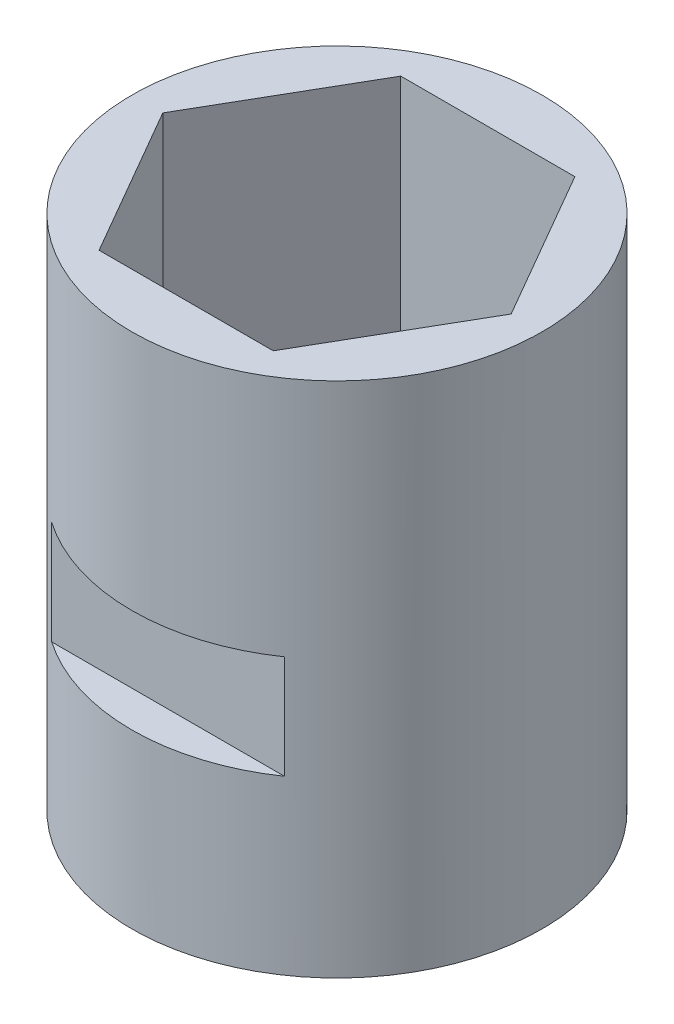
SolidWorks part; units mm, degrees
ref_plane "Front Plane" through (0, 0, 0) normal (0, 0, 1) x (1, 0, 0)
ref_plane "Top Plane" through (0, 0, 0) normal (0, 1, 0) x (1, 0, 0)
ref_plane "Right Plane" through (0, 0, 0) normal (1, 0, 0) x (0, 0, -1)
sketch "Sketch1" plane through (0, 0, 0) normal (0, 1, 0) x (1, 0, 0)
  line L1 (-3.2079, 5.5563) -> (-6.4158, 0)
  line L2 (-6.4158, 0) -> (-3.2079, -5.5562)
  line L3 (-3.2079, -5.5562) -> (3.2079, -5.5562)
  line L4 (3.2079, -5.5562) -> (6.4158, 0)
  line L5 (6.4158, 0) -> (3.2079, 5.5563)
  line L6 (3.2079, 5.5563) -> (-3.2079, 5.5563)
  circle A0 centre (0, 0) radius 5.5562 construction
  circle A1 centre (0, 0) radius 7.5565
  point P1 (0, 0)
  point P11 (0, 0)
  point P12 (0, 0)
  dimension "D2" = 15.113
  dimension "D1" = 11.1125
extrude "Boss-Extrude1" add sketch "Sketch1" along normal blind 15.875
sketch "Sketch2" plane through (0, 0, 0) normal (0, -1, 0) x (1, 0, 0)
  circle A0 centre (0, 0) radius 7.5565
  circle A1 centre (0, 0) radius 3.3782
  dimension "D1" = 6.7564
extrude "Boss-Extrude2" add sketch "Sketch2" along normal blind 3.175
sketch "Sketch3" plane through (0, 0, 0) normal (1, 0, 0) x (0, 0, -1)
  line L0 (-6.223, 6.985) -> (-6.223, 3.175)
  line L1 (6.223, 6.985) -> (6.223, 3.175)
  line L2 (-7.5565, -3.175) -> (7.5565, -3.175) construction
  line L3 (-6.223, 6.985) -> (-8.202, 6.985)
  line L4 (-8.202, 6.985) -> (-8.202, 3.175)
  line L5 (-8.202, 3.175) -> (-6.223, 3.175)
  line L6 (6.223, 6.985) -> (8.4791, 6.985)
  line L7 (8.4791, 6.985) -> (8.4791, 3.175)
  line L8 (8.4791, 3.175) -> (6.223, 3.175)
  dimension "D1" = 12.446
  dimension "D2" = 6.223
  dimension "D3" = 3.81
  dimension "D4" = 3.81
  dimension "D5" = 6.35
  dimension "D6" = 6.35
extrude "Cut-Extrude1" cut sketch "Sketch3" against normal through all and the other way through all
